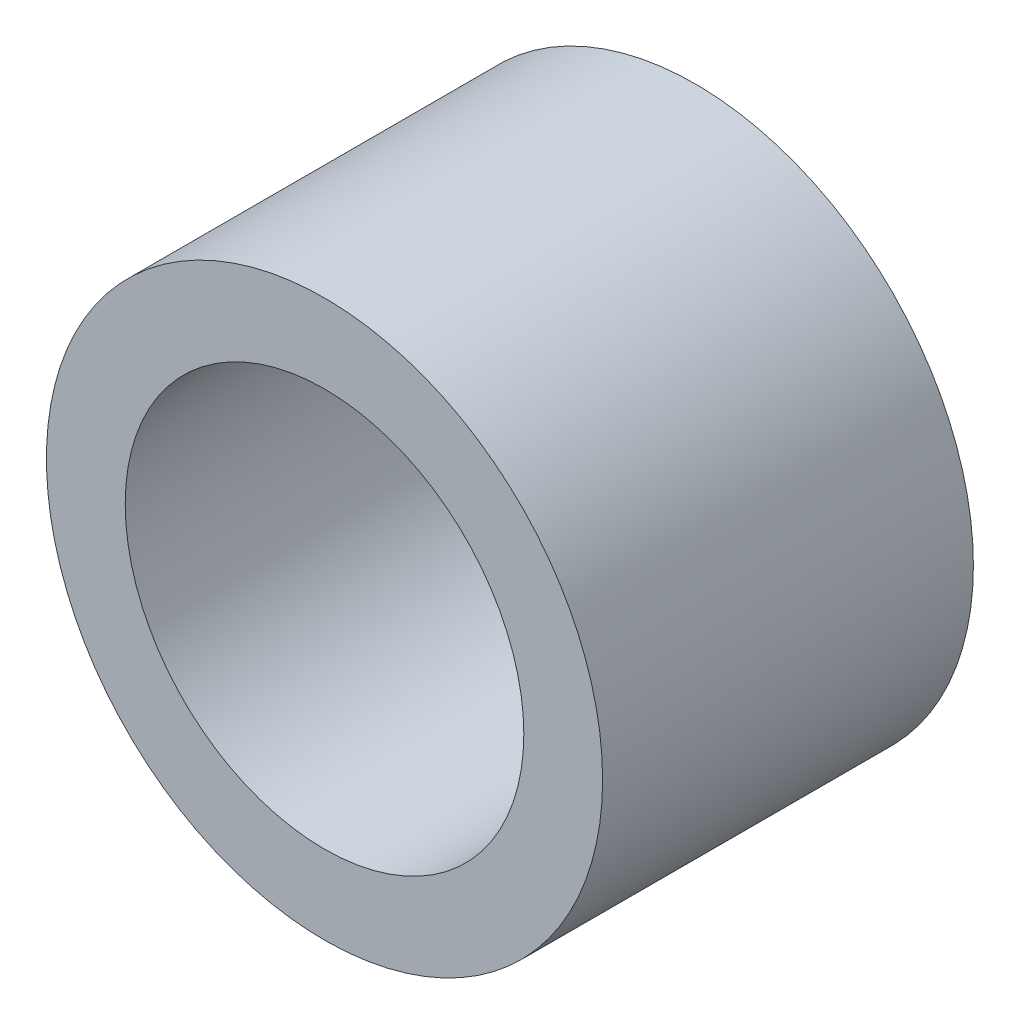
SolidWorks part; units mm, degrees
ref_plane "Front Plane" through (0, 0, 0) normal (0, 0, 1) x (1, 0, 0)
ref_plane "Top Plane" through (0, 0, 0) normal (0, 1, 0) x (1, 0, 0)
ref_plane "Right Plane" through (0, 0, 0) normal (1, 0, 0) x (0, 0, -1)
sketch "Sketch1" plane through (0, 0, 0) normal (0, 0, 1) x (1, 0, 0)
  circle A0 centre (0, 0) radius 3
  circle A1 centre (0, 0) radius 2.15
  dimension "OD" = 6
  dimension "ID" = 4.3
extrude "Extrude1" add sketch "Sketch1" along normal mid plane 4
sketch "Sketch2" plane through (0, 0, 0) normal (1, 0, 0) x (0, 0, -1)
  line L0 (-2, -2.15) -> (2, -2.15) construction
  line L3 (2, 2.15) -> (-2, 2.15) construction
  line L5 (-2, -2.15) -> (2, -2.15)
  line L6 (2, 2.15) -> (-2, 2.15)
sketch "Sketch4" plane through (0, 0, 2) normal (0, 0, 1) x (1, 0, 0)
  line L0 (0, 0) -> (-1.5203, 1.5203)
  line L1 (0, -1.65) -> (0, 1.65) construction
  circle A0 centre (0, 0) radius 2.15 construction
  dimension "D1" = 45
